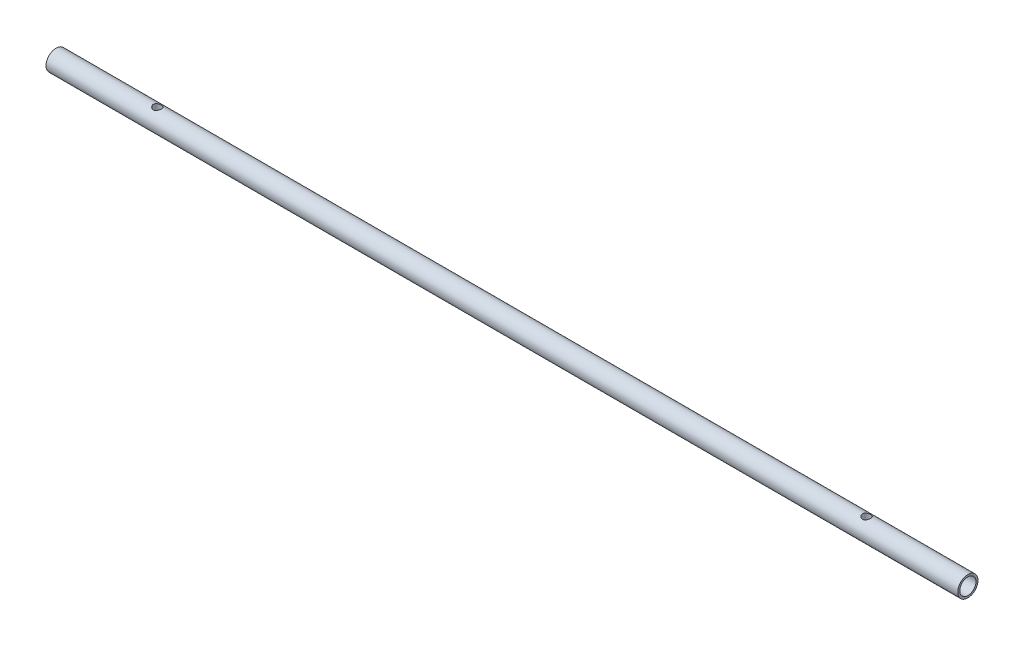
SolidWorks part; units mm, degrees
ref_plane "Front Plane" through (0, 0, 0) normal (1, 0, 0) x (0, 1, 0)
ref_plane "Top Plane" through (0, 0, 0) normal (0, 0, 1) x (0, 1, 0)
ref_plane "Right Plane" through (0, 0, 0) normal (0, 1, 0) x (-1, 0, 0)
sketch "Sketch1" plane through (0, 0, 0) normal (1, 0, 0) x (0, 1, 0)
  circle A0 centre (0, 0) radius 10
  dimension "D1" = 20
extrude "Boss-Extrude1" add sketch "Sketch1" along normal blind 900
sketch "Sketch2" plane through (900, 0, 0) normal (1, 0, 0) x (0, 1, 0)
  circle A0 centre (0, 0) radius 8
  dimension "D1" = 16
extrude "Cut-Extrude1" cut sketch "Sketch2" against normal blind 40
sketch "Sketch3" plane through (0, 0, 0) normal (-1, 0, 0) x (0, -1, 0)
  circle A0 centre (0, 0) radius 8
  dimension "D1" = 16
extrude "Cut-Extrude2" cut sketch "Sketch3" against normal blind 40
sketch "Sketch4" plane through (0, 0, 0) normal (0, 1, 0) x (-1, 0, 0)
  line L0 (-450, 10) -> (-450, -10) construction
  line L1 (0, 10) -> (-900, 10) construction
  line L2 (-900, -10) -> (0, -10) construction
  line L3 (-450, 0) -> (-100, 0) construction
  circle A0 centre (-100, 0) radius 4
  circle A1 centre (-800, 0) radius 4
  dimension "D2" = 8
  dimension "D1" = 350
extrude "Cut-Extrude3" cut sketch "Sketch4" against normal blind 40 and the other way blind 40
